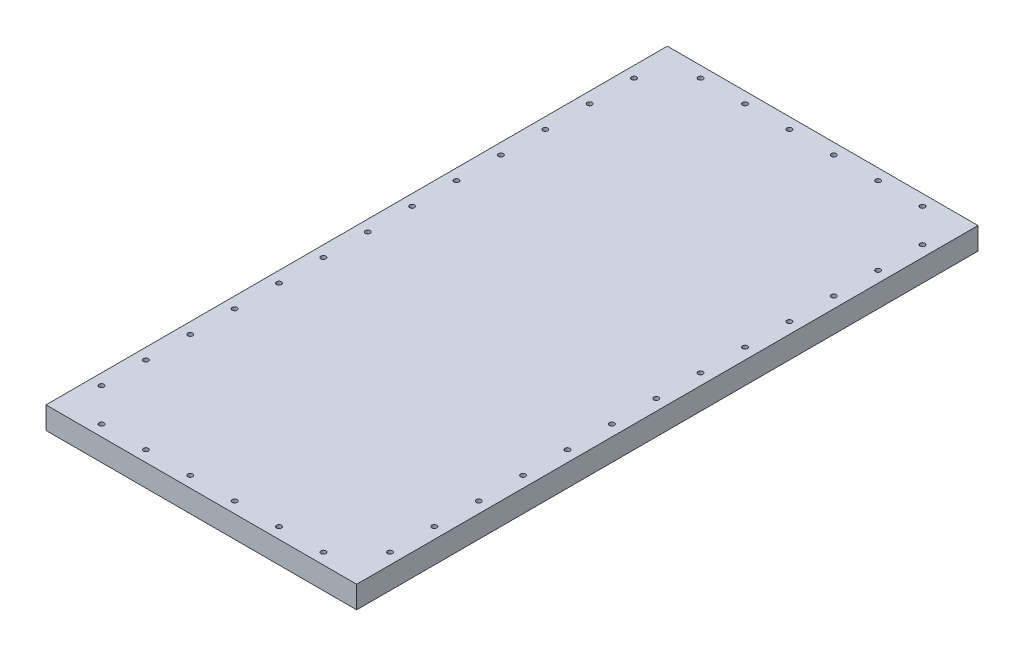
SolidWorks part; units mm, degrees
ref_plane "Front Plane" through (0, 0, 0) normal (0, 0, 1) x (1, 0, 0)
ref_plane "Top Plane" through (0, 0, 0) normal (0, 1, 0) x (1, 0, 0)
ref_plane "Right Plane" through (0, 0, 0) normal (1, 0, 0) x (0, 0, -1)
sketch "Sketch1" plane through (0, 0, 0) normal (0, 0, 1) x (1, 0, 0)
  line L1 (266.7, -19.05) -> (-266.7, -19.05)
  line L2 (266.7, -19.05) -> (266.7, 19.05)
  line L3 (266.7, 19.05) -> (-266.7, 19.05)
  line L4 (-266.7, -19.05) -> (-266.7, 19.05)
  line L5 (266.7, -19.05) -> (-266.7, 19.05) construction
  line L6 (266.7, 19.05) -> (-266.7, -19.05) construction
  point P0 (0, 0)
  dimension "D1" = 38.1
  dimension "D2" = 533.4
extrude "Boss-Extrude1" add sketch "Sketch1" along normal blind 1066.8
hole_wizard "CSK for 5/16 Flat Head Machine Screw1" positions "Sketch2" profile "Sketch3" countersink size "5/16" standard "ANSI Inch" end condition through all
sketch "Sketch2" plane through (0, -19.05, 0) normal (0, -1, 0) x (-1, 0, 0)
  line L0 (266.7, -1066.8) -> (-266.7, -1066.8) construction
  line L1 (266.7, -1066.8) -> (266.7, 0) construction
  line L3 (266.7, 0) -> (-266.7, 0) construction
  point P0 (190.5, -1047.75)
  point P66 (114.3, -1047.75)
  point P67 (38.1, -1047.75)
  point P68 (-38.1, -1047.75)
  point P69 (-114.3, -1047.75)
  point P70 (-190.5, -1047.75)
  point P71 (114.3, -19.05)
  point P72 (38.1, -19.05)
  point P73 (-38.1, -19.05)
  point P74 (-114.3, -19.05)
  point P75 (-190.5, -19.05)
  point P76 (190.5, -19.05)
  dimension "D1" = 19.05
  dimension "D2" = 76.2
  dimension "D5" = 19.05
  dimension "D3" = 6
  dimension "D4" = 2
sketch "Sketch3" plane through (-190.5, -19.05, 1047.75) normal (1, 0, 0) x (0, 0, -1)
  line L0 (0, 0) -> (0, 38.1)
  line L1 (0, 38.1) -> (4.2164, 38.1)
  line L2 (4.2164, 38.1) -> (4.2164, 4.4267)
  line L3 (4.2164, 4.4267) -> (8.0645, 0)
  line L5 (8.0645, 0) -> (0, 0)
  line L6 (-4.2164, 4.4267) -> (-8.0645, 0) construction
  line L11 (0, -6.35) -> (0, 107.95) construction
  dimension "Thru Hole Dia." = 8.4328
  dimension "Thru Hole Depth" = 38.1
  dimension "Near C'Sink Dia." = 16.129
  dimension "Near C'Sink Angle" = 82
hole_wizard "CSK for 5/16 Flat Head Machine Screw2" positions "Sketch4" profile "Sketch5" countersink size "5/16" standard "ANSI Inch" end condition through all
sketch "Sketch4" plane through (0, -19.05, 0) normal (0, -1, 0) x (-1, 0, 0)
  line L0 (-266.7, -1066.8) -> (-266.7, 0) construction
  line L1 (266.7, 0) -> (-266.7, 0) construction
  point P0 (-247.65, -76.2)
  point P13 (-247.65, -152.4)
  point P14 (-247.65, -228.6)
  point P15 (-247.65, -304.8)
  point P16 (-247.65, -381)
  point P17 (-247.65, -457.2)
  point P18 (-247.65, -533.4)
  point P19 (-247.65, -609.6)
  point P20 (-247.65, -685.8)
  point P21 (-247.65, -762)
  point P37 (247.65, -76.2)
  point P38 (247.65, -152.4)
  point P39 (247.65, -228.6)
  point P40 (247.65, -304.8)
  point P41 (247.65, -381)
  point P42 (247.65, -457.2)
  point P43 (247.65, -533.4)
  point P44 (247.65, -609.6)
  point P45 (247.65, -685.8)
  point P46 (247.65, -762)
  point P54 (-247.65, -838.2)
  point P55 (247.65, -838.2)
  point P56 (-247.65, -914.4)
  point P57 (247.65, -914.4)
  point P58 (-247.65, -990.6)
  point P59 (247.65, -990.6)
  dimension "D1" = 19.05
  dimension "D2" = 76.2
  dimension "D4" = 76.2
  dimension "D5" = 2
  dimension "D6" = 495.3
  dimension "D7" = 4
  dimension "D8" = 76.2
  dimension "D3" = 10
sketch "Sketch5" plane through (247.65, -19.05, 76.2) normal (1, 0, 0) x (0, 0, -1)
  line L0 (0, 0) -> (0, 38.1)
  line L1 (0, 38.1) -> (4.2164, 38.1)
  line L2 (4.2164, 38.1) -> (4.2164, 4.4267)
  line L3 (4.2164, 4.4267) -> (8.0645, 0)
  line L5 (8.0645, 0) -> (0, 0)
  line L6 (-4.2164, 4.4267) -> (-8.0645, 0) construction
  line L11 (0, -6.35) -> (0, 107.95) construction
  dimension "Thru Hole Dia." = 8.4328
  dimension "Thru Hole Depth" = 38.1
  dimension "Near C'Sink Dia." = 16.129
  dimension "Near C'Sink Angle" = 82
